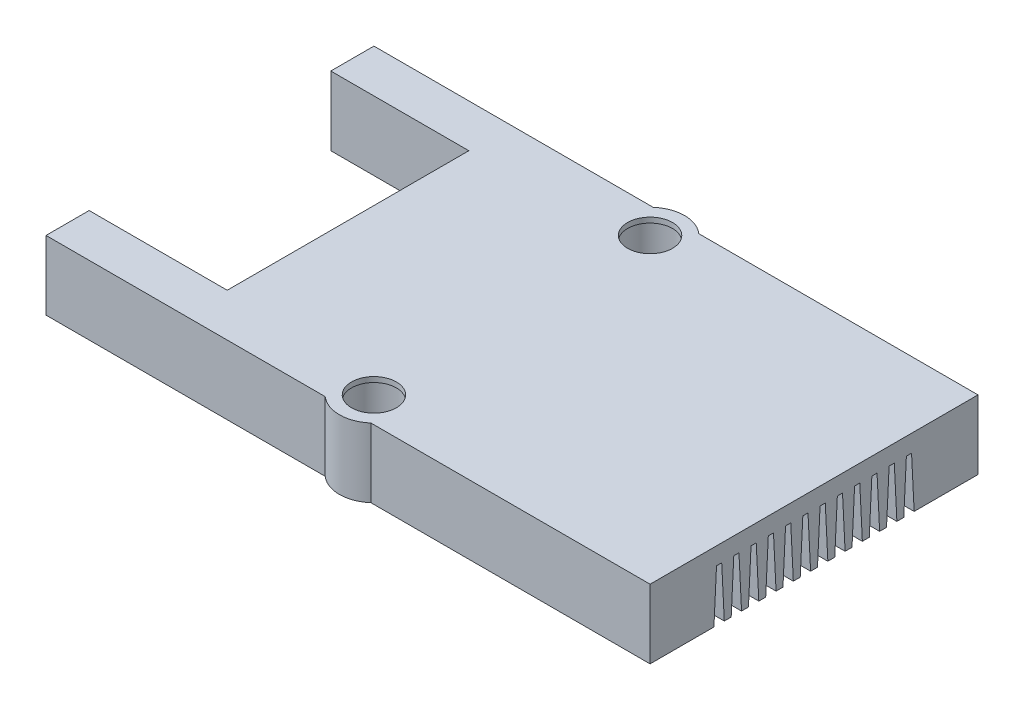
SolidWorks part; units mm, degrees
material "6061 Alloy"
ref_plane "Спереди" through (0, 0, 0) normal (0, 0, 1) x (1, 0, 0)
ref_plane "Сверху" through (0, 0, 0) normal (0, 1, 0) x (1, 0, 0)
ref_plane "Справа" through (0, 0, 0) normal (1, 0, 0) x (0, 0, -1)
other "Configuration Table"
sketch "Sketch1" plane through (0, 0, 0) normal (0, 1, 0) x (1, 0, 0)
  line L0 (-150.9972, 0) -> (170.9402, 0) construction
  line L1 (-175, 95) -> (-13.2288, 95)
  line L2 (-175, 95) -> (-175, -95)
  line L3 (-175, -95) -> (-13.2288, -95)
  line L4 (175, 95) -> (175, -95)
  line L5 (-175, 95) -> (175, -95) construction
  line L6 (-175, -95) -> (175, 95) construction
  line L7 (13.2288, 95) -> (175, 95)
  line L8 (13.2288, -95) -> (175, -95)
  line L10 (-175, 70) -> (-95, 70)
  line L11 (-175, 70) -> (-175, -70)
  line L12 (-175, -70) -> (-95, -70)
  line L13 (-95, 70) -> (-95, -70)
  circle A0 centre (0, 80) radius 15
  circle A1 centre (0, -80) radius 15
  arc A2 (-13.2288, 95) -> (13.2288, 95) centre (0, 80) cw
  arc A3 (-13.2288, -95) -> (13.2288, -95) centre (0, -80) ccw
  circle A4 centre (0, 80) radius 13
  circle A5 centre (0, -80) radius 13
  arc A6 (13.2288, 95) -> (-13.2288, 95) centre (0, 80) ccw
  arc A7 (-13.2288, -95) -> (13.2288, -95) centre (0, -80) ccw
  point P0 (0, 0)
  dimension "D3" = 30
  dimension "D4" = 5
  dimension "D5" = 2
  dimension "D6" = 140
  dimension "D1" = 160
  dimension "D2" = 350
  dimension "D7" = 80
extrude "Boss-Extrude2" add sketch "Sketch1" against normal blind 40 contours L3 A3 L8 L4 L7 A2 L1 L2 A0 A1 region at (27.965, 0, 0)
extrude "Boss-Extrude3" add sketch "Sketch1<4>" against normal blind 3 contours A0 A4 | A1 A5 region at (-14.5757, 0, -80) region at (-14.5757, 0, 80)
sketch "Sketch1<4>" plane through (0, 0, 0) normal (0, 1, 0) x (1, 0, 0) same geometry as "Sketch1"
sketch "Sketch3" plane through (-95, 0, 0) normal (-1, 0, 0) x (0, 0, 1)
  line L0 (-58, -40) -> (-56.5, -10)
  line L1 (-70, -40) -> (70, -40) construction
  line L2 (-56.5, -10) -> (-53.5, -10)
  line L3 (-53.5, -10) -> (-52, -40)
  line L4 (-58, -40) -> (-52, -40)
  line L5 (-55, 8.1645) -> (-55, -51.3984) construction
  line L6 (-48, -40) -> (-46.5, -10)
  line L7 (-70, 0) -> (70, 0) construction
  line L8 (-46.5, -10) -> (-43.5, -10)
  line L9 (-43.5, -10) -> (-42, -40)
  line L10 (-48, -40) -> (-42, -40)
  line L11 (-45, 8.1645) -> (-45, -51.3984) construction
  line L12 (-38, -40) -> (-36.5, -10)
  line L13 (-36.5, -10) -> (-33.5, -10)
  line L14 (-33.5, -10) -> (-32, -40)
  line L15 (-38, -40) -> (-32, -40)
  line L16 (-35, 8.1645) -> (-35, -51.3984) construction
  line L17 (-28, -40) -> (-26.5, -10)
  line L18 (-26.5, -10) -> (-23.5, -10)
  line L19 (-23.5, -10) -> (-22, -40)
  line L20 (-28, -40) -> (-22, -40)
  line L21 (-25, 8.1645) -> (-25, -51.3984) construction
  line L22 (-18, -40) -> (-16.5, -10)
  line L23 (-16.5, -10) -> (-13.5, -10)
  line L24 (-13.5, -10) -> (-12, -40)
  line L25 (-18, -40) -> (-12, -40)
  line L26 (-15, 8.1645) -> (-15, -51.3984) construction
  line L27 (-8, -40) -> (-6.5, -10)
  line L28 (-6.5, -10) -> (-3.5, -10)
  line L29 (-3.5, -10) -> (-2, -40)
  line L30 (-8, -40) -> (-2, -40)
  line L31 (-5, 8.1645) -> (-5, -51.3984) construction
  line L32 (2, -40) -> (3.5, -10)
  line L33 (3.5, -10) -> (6.5, -10)
  line L34 (6.5, -10) -> (8, -40)
  line L35 (2, -40) -> (8, -40)
  line L36 (5, 8.1645) -> (5, -51.3984) construction
  line L37 (12, -40) -> (13.5, -10)
  line L38 (13.5, -10) -> (16.5, -10)
  line L39 (16.5, -10) -> (18, -40)
  line L40 (12, -40) -> (18, -40)
  line L41 (15, 8.1645) -> (15, -51.3984) construction
  line L42 (22, -40) -> (23.5, -10)
  line L43 (23.5, -10) -> (26.5, -10)
  line L44 (26.5, -10) -> (28, -40)
  line L45 (22, -40) -> (28, -40)
  line L46 (25, 8.1645) -> (25, -51.3984) construction
  line L47 (32, -40) -> (33.5, -10)
  line L48 (33.5, -10) -> (36.5, -10)
  line L49 (36.5, -10) -> (38, -40)
  line L50 (32, -40) -> (38, -40)
  line L51 (35, 8.1645) -> (35, -51.3984) construction
  line L52 (42, -40) -> (43.5, -10)
  line L53 (43.5, -10) -> (46.5, -10)
  line L54 (46.5, -10) -> (48, -40)
  line L55 (42, -40) -> (48, -40)
  line L56 (45, 8.1645) -> (45, -51.3984) construction
  line L57 (52, -40) -> (53.5, -10)
  line L58 (53.5, -10) -> (56.5, -10)
  line L59 (56.5, -10) -> (58, -40)
  line L60 (52, -40) -> (58, -40)
  line L61 (55, 8.1645) -> (55, -51.3984) construction
  point P11 (0, 0)
  dimension "D1" = 6
  dimension "D2" = 3
  dimension "D3" = 10
  dimension "D4" = 55
  dimension "D6" = 10
  dimension "D5" = 12
extrude "Cut-Extrude1" cut sketch "Sketch3" against normal through all
